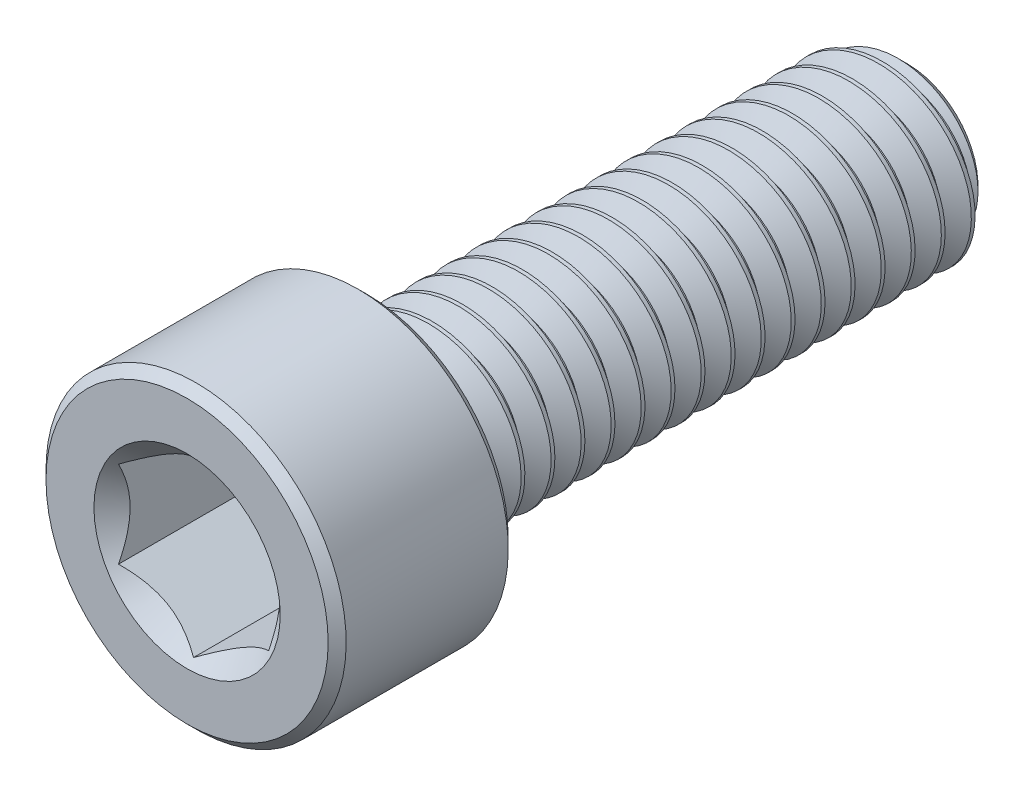
SolidWorks part; units mm, degrees
ref_plane "Front Plane" through (0, 0, 0) normal (0, 0, 1) x (1, 0, 0)
ref_plane "Top Plane" through (0, 0, 0) normal (0, 1, 0) x (1, 0, 0)
ref_plane "Right Plane" through (0, 0, 0) normal (1, 0, 0) x (0, 0, -1)
sketch "Sketch1" plane through (0, 0, 0) normal (1, 0, 0) x (0, 0, -1)
  line L0 (-12, 0) -> (12, 0) construction
  line L1 (12, 0) -> (12, 2.3505) construction
  line L2 (12, 2.3505) -> (11.3505, 3) construction
  line L3 (11.3505, 3) -> (11.25, 3) construction
  line L4 (11.25, 3) -> (-6, 3) construction
  line L5 (-6, 3) -> (-6, 5) construction
  line L6 (-6, 5) -> (-12, 5) construction
  line L7 (-12, 5) -> (-12, 0) construction
  line L8 (12, 2.3505) -> (12, 3) construction
  line L9 (11.9375, 3.1083) -> (12.4375, 2.2422) construction
  line L10 (12.4375, 2.2422) -> (12.9375, 3.1083) construction
  line L11 (12.9375, 3.1083) -> (11.9375, 3.1083) construction
  line L12 (12.4375, 3.1083) -> (12.4375, 3) construction
  line L13 (12.4375, 2.2422) -> (12.4375, 2.3505) construction
  line L14 (12.375, 2.3505) -> (12.5, 2.3505) construction
  line L15 (12, 3) -> (12.875, 3) construction
  line L16 (11.9688, 3.0541) -> (12.9062, 3.0541) construction
  line L17 (12, 0) -> (12, -3) construction
  line L18 (-6.3, 5) -> (-6, 4.7) construction
  line L19 (-11.7, 5) -> (-12, 4.7) construction
  line L20 (-6, 3) -> (-6, 0) construction
  line L21 (-6, 1.5) -> (0, 1.5) construction
  line L22 (0, 1.5) -> (6, 1.5) construction
  line L23 (6, 1.5) -> (12, 1.5) construction
  line L24 (0, 1.5) -> (0, 3) construction
  line L25 (0, 3) -> (0, 5) construction
  line L26 (6, 1.5) -> (6, 5) construction
  point P0 (-12, 2.5)
  point P3 (9.5, 3)
  point P4 (0, 0)
  point P18 (6, 3)
  point P22 (12.4375, 2.3505)
  point P24 (11.25, 3)
  point P25 (12.4375, 3)
  point P28 (12.4375, 3.0541)
  point P29 (9.5, -3)
  point P30 (0, 3)
  point P31 (-9, 5)
  point P37 (-7.05, 5)
  point P38 (-11.55, 5)
  point P45 (0, 1.5)
  point P46 (6, 1.5)
  dimension "D2" = 0.125
  dimension "D7" = 0.3
  dimension "D8" = 0.3
  dimension "D9" = 0.3
  dimension "D10" = 0.15
  dimension "D11" = 0.75
  dimension "Drive Size" = 5
  dimension "Head Diameter" = 10
  dimension "Head Height" = 6
  dimension "Thread Pitch" = 1
  dimension "Thread Dia" = 6
  dimension "Length" = 18
  dimension "D12" = 0.75
  dimension "D4" = 2.5
  dimension "D3" = 45
sketch "Sketch2" plane through (0, 0, 0) normal (1, 0, 0) x (0, 0, -1)
  line L0 (-12, 0) -> (-12, 4.7)
  line L1 (-11.7, 5) -> (-6.3, 5)
  line L2 (-6, 4.7) -> (-6, 3.3)
  line L4 (11.3505, 3) -> (12, 2.3505)
  line L5 (12, 2.3505) -> (12, 0)
  line L6 (-6, 5) -> (-12, 5) construction
  line L7 (12, 0) -> (-12, 0)
  line L8 (-11.7, 5) -> (-12, 4.7) construction
  line L10 (-11.7, 5) -> (-12, 4.7)
  line L14 (-6.3, 5) -> (-6, 4.7) construction
  line L16 (-6.3, 5) -> (-6, 4.7)
  line L17 (-6, 3) -> (-6, 5) construction
  line L19 (-5.7, 3) -> (11.3505, 3)
  line L20 (11.25, 3) -> (-6, 3) construction
  arc A1 (-6, 3.3) -> (-5.7, 3) centre (-5.7, 3.3) ccw
  dimension "D3" = 0.3
revolve "Revolve1" add sketch "Sketch2" angle 360 about L7
sketch "Sketch3" plane through (0, 0, 12) normal (0, 0, 1) x (1, 0, 0)
  line L1 (2.5, -1.4434) -> (2.5, 1.4434)
  line L2 (2.5, 1.4434) -> (0, 2.8868)
  line L3 (0, 2.8868) -> (-2.5, 1.4434)
  line L4 (-2.5, 1.4434) -> (-2.5, -1.4434)
  line L5 (-2.5, -1.4434) -> (0, -2.8868)
  line L6 (0, -2.8868) -> (2.5, -1.4434)
  circle A0 centre (0, 0) radius 2.5 construction
  circle A1 centre (0, 0) radius 5 construction
  circle A2 centre (0, 0) radius 5 construction
  circle A3 centre (0, 0) radius 2.8868 construction
  point P13 (0, 0)
  dimension "D1" = 5.7735
extrude "Cut-Extrude1" cut sketch "Sketch3" against normal offset from surface (5 mm away) 1 up to face at (0, 4.7, 6)
sketch "Sketch4" plane through (0, 0, 12) normal (0, 0, 1) x (1, 0, 0)
  circle A0 centre (0, 0) radius 3.1033
  dimension "D1" = 6.2065
extrude "Cut-Extrude2" cut sketch "Sketch4" against normal up to vertex (3 mm away) draft 45 up to point (0, 5, 9)
sketch "Sketch11" plane through (0, 0, 0) normal (1, 0, 0) x (0, 0, -1)
  line L0 (-12, 0) -> (12, 0) construction
  line L1 (-12, 0) -> (12, 0) construction
  line L2 (-2.625, 0) -> (-2.625, 3) construction
  line L3 (11.25, 3) -> (-6, 3) construction
  line L4 (8.625, 0) -> (8.625, 3) construction
  line L6 (12, 2.3505) -> (12, 3) construction
  point P2 (-2.625, 0)
  point P3 (8.625, 0)
  dimension "D1" = 3.375
  dimension "D2" = 3.375
sketch "Sketch6" plane through (0, 0, -12) normal (0, 0, -1) x (-1, 0, 0)
  circle A0 centre (0, 0) radius 3
curve "Helix/Spiral1" pitch 1 height 19 turns 19
sketch "Sketch10" plane through (0, 0, 0) normal (1, 0, 0) x (0, 0, -1)
  line L0 (-5.7, -5) -> (-5.7, 5)
  line L5 (-12, 0) -> (12, 0) construction
  line L6 (-5.7, 3) -> (-5.7, -3) construction
  point P3 (-5.7, 0)
split "Split1" trim tools "Sketch10" bodies to split 106 resulting bodies 114 115
sketch "Sketch7" plane through (0, 0, 0) normal (1, 0, 0) x (0, 0, -1)
  line L0 (11.9688, 3.0541) -> (12.9062, 3.0541)
  line L1 (12.9062, 3.0541) -> (12.5, 2.3505)
  line L2 (12.5, 2.3505) -> (12.375, 2.3505)
  line L3 (12.375, 2.3505) -> (11.9688, 3.0541)
sweep "Cut-Sweep1" cut profiles "Sketch7" path "Helix/Spiral1" align with end faces yes
sketch "Sketch8" plane through (0, 0, 0) normal (1, 0, 0) x (0, 0, -1)
  line L0 (-6, 0) -> (-6, 3)
  line L1 (-5.7, -3) -> (-5.7, 3) construction
  line L2 (-6, 3) -> (-5.7, 3)
  line L4 (-5.7, 3) -> (-3.9679, 0)
  line L5 (-3.9679, 0) -> (-6, 0)
  line L6 (11.25, 3) -> (-6, 3) construction
  line L7 (-12, 0) -> (12, 0) construction
  dimension "D1" = 60
revolve "Revolve2" add sketch "Sketch8" angle 360 about L5
equation "\"D2@Sketch1\" = \"Thread Pitch@Sketch1\" / 8"
equation "\"D4@Helix/Spiral1\" = \"Thread Pitch@Sketch1\""
equation "\"D7@Sketch1\" = \"Head Height@Sketch1\" * .05"
equation "\"D8@Sketch1\"=\"D7@Sketch1\""
equation "\"D9@Sketch1\"=\"D7@Sketch1\""
equation "\"D10@Sketch1\"=\"D7@Sketch1\"/2"
equation "\"D11@Sketch1\"=\"D10@Sketch1\"*5"
equation "\"D4@Sketch1\"=\"Thread Pitch@Sketch1\"*2.5"
equation "\"D12@Sketch1\"=\"Thread Pitch@Sketch1\"*.75"
equation "\"D3@Helix/Spiral1\"=\"Length@Sketch1\"+\"Thread Pitch@Sketch1\""
equation "\"D3@Sketch2\"=\"Thread Dia@Sketch1\"*0.05"
equation "\"D1@Sketch11\"=\"Length@Sketch1\"*0.1875"
equation "\"D2@Sketch11\"=\"D1@Sketch11\""
equation "\"D1@Sketch4\"=\"D1@Sketch3\"*1.075"
